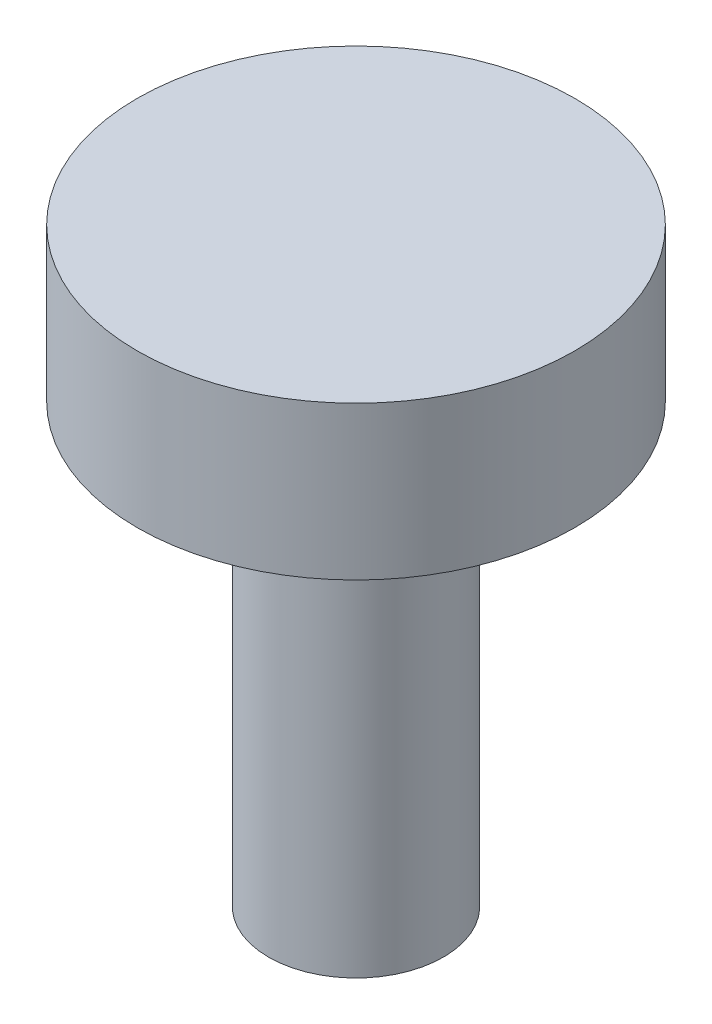
SolidWorks part; units mm, degrees
ref_plane "Front Plane" through (0, 0, 0) normal (0, 0, 1) x (1, 0, 0)
ref_plane "Top Plane" through (0, 0, 0) normal (0, 1, 0) x (1, 0, 0)
ref_plane "Right Plane" through (0, 0, 0) normal (1, 0, 0) x (0, 0, -1)
sketch "Sketch1" plane through (0, 0, 0) normal (0, 1, 0) x (1, 0, 0)
  circle A0 centre (0, 0) radius 10
  circle A1 centre (0, 0) radius 4
  dimension "D1" = 20
  dimension "D2" = 8
extrude "Boss-Extrude1" add sketch "Sketch1" along normal blind 7 contours A1 | A0 A1 region at (-9.7172, 0, 0) region at (0, 0, 0)
extrude "Boss-Extrude2" add sketch "Sketch1<3>" against normal blind 20 contours A1 region at (0, 0, 0)
sketch "Sketch1<3>" plane through (0, 0, 0) normal (0, 1, 0) x (1, 0, 0) same geometry as "Sketch1"
